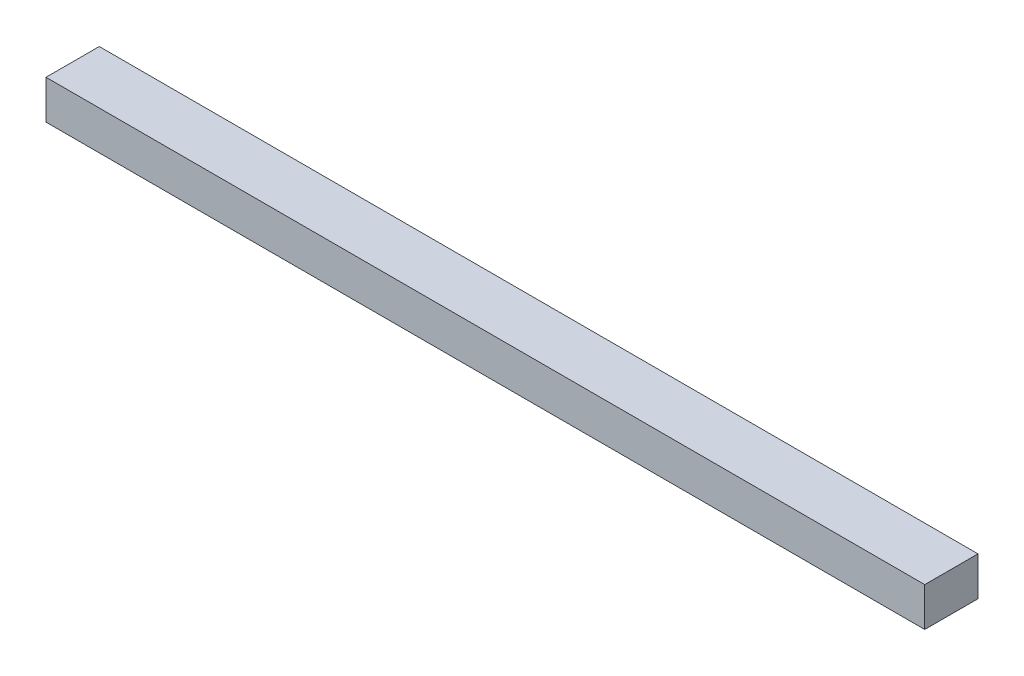
SolidWorks part; units mm, degrees
ref_plane "Face" through (0, 0, 0) normal (0, 0, 1) x (1, 0, 0)
ref_plane "Dessus" through (0, 0, 0) normal (0, 1, 0) x (1, 0, 0)
ref_plane "Droite" through (0, 0, 0) normal (1, 0, 0) x (0, 0, -1)
sketch "Sketch1" plane through (0, 0, 0) normal (0, 1, 0) x (1, 0, 0)
  line L1 (20.955, -1.27) -> (-20.955, -1.27)
  line L2 (20.955, -1.27) -> (20.955, 1.27)
  line L3 (20.955, 1.27) -> (-20.955, 1.27)
  line L4 (-20.955, -1.27) -> (-20.955, 1.27)
  line L5 (20.955, -1.27) -> (-20.955, 1.27) construction
  line L6 (20.955, 1.27) -> (-20.955, -1.27) construction
  point P0 (0, 0)
  dimension "D1" = 41.91
  dimension "D2" = 2.54
extrude "Boss-Extrude1" add sketch "Sketch1" along normal blind 1.8542
